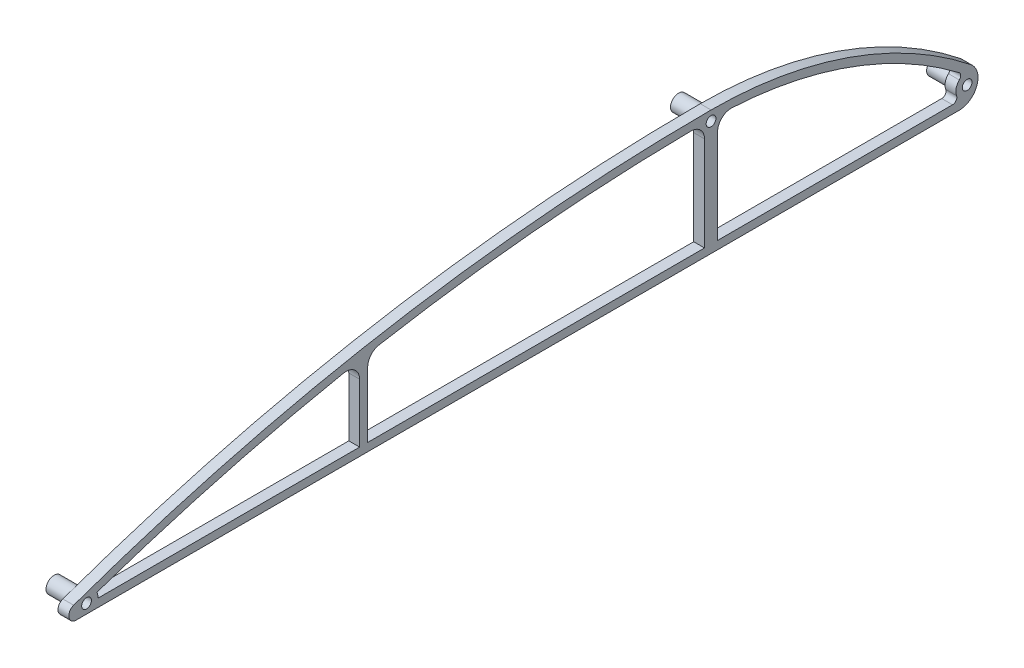
SolidWorks part; units mm, degrees
other "Marquage1"
sketch "Esquisse8" plane through (8, 0, -172.8424) normal (1, 0, 0) x (0, 0, -1)
other "Marquage2"
sketch "Esquisse10" plane through (-6, 20, -172.8424) normal (-0.8365, 0.2588, -0.483) x (-0.5, 0, 0.866)
other "Marquage3"
sketch "Esquisse11" plane through (0, 0, 0) normal (-0.0501, -0.1345, 0.9896) x (0.9942, 0.0873, 0.0622)
ref_plane "Plan de face" through (0, 0, 0) normal (0, 0, 1) x (1, 0, 0)
ref_plane "Plan de dessus" through (0, 0, 0) normal (0, 1, 0) x (1, 0, 0)
ref_plane "Plan de droite" through (0, 0, 0) normal (1, 0, 0) x (0, 0, -1)
sketch "Esquisse2" plane through (0, 0, 0) normal (1, 0, 0) x (0, 0, -1)
  line L0 (0, 0) -> (170.8732, 0)
  arc A1 (173.0499, 6.2408) -> (125, 23) centre (125, -54.2609) ccw
  arc A3 (170.8732, 0) -> (173.0499, 6.2408) centre (170.8732, 3.5) ccw
  arc A4 (125, 23) -> (0, 0) centre (125, -328.1739) ccw
  point P10 (180, 0)
  dimension "D1" = 180
  dimension "D2" = 3.5
  dimension "D3" = 23
  dimension "D4" = 55
extrude "Boss.-Extru.1" add sketch "Esquisse2" along normal blind 2
sketch "Esquisse4" plane through (2, 0, 0) normal (1, 0, 0) x (0, 0, -1)
  line L0 (9.5, 0) -> (9.5, 3.4627) construction
  line L1 (0, 0) -> (9.5, 1.7314) construction
  line L10 (174.369, 3.3283) -> (172.369, 3.3283) construction
  line L11 (0, 0) -> (170.8732, 0) construction
  circle A6 centre (125, 21.2) radius 0.9
  circle A12 centre (172.369, 3.3283) radius 0.9
  arc A13 (170.8732, 0) -> (173.0499, 6.2408) centre (170.8732, 3.5) ccw construction
  circle A15 centre (9.5, 1.7314) radius 0.9
  arc A16 (125, 23) -> (0, 0) centre (125, -328.1739) ccw construction
  dimension "D1" = 1.8
  dimension "D2" = 1.8
  dimension "D7" = 1.8
  dimension "D3" = 1.8
  dimension "D4" = 9.5
  dimension "D6" = 2
extrude "Enlèv. mat.-Extru.2" cut sketch "Esquisse4" against normal through all
sketch "Esquisse9" plane through (0, 0, 0) normal (1, 0, 0) x (0, 0, -1)
  line L26 (126.214, 1.5) -> (171.3359, 1.5)
  line L35 (8.4369, 1.5) -> (170.8732, 1.5)
  line L36 (11.5872, 1.5) -> (60, 1.5)
  line L40 (61.5, 1.5) -> (123.786, 1.5)
  line L42 (60, 1.5) -> (60, 15.4055)
  line L44 (61.5, 1.5) -> (61.5, 15.6859)
  line L45 (123.786, 21.4979) -> (123.786, 1.5)
  line L46 (126.214, 21.4979) -> (126.214, 1.5)
  arc A20 (60, 15.4055) -> (11.4359, 2.5451) centre (125, -328.1739) ccw
  circle A21 centre (125, 21.2) radius 0.9 construction
  circle A22 centre (9.5, 1.7314) radius 0.9 construction
  arc A23 (173.0499, 6.2408) -> (125, 23) centre (125, -54.2609) ccw construction
  arc A25 (171.778, 5.3435) -> (171.3359, 1.5) centre (172.369, 3.3283) ccw
  circle A26 centre (172.369, 3.3283) radius 0.9 construction
  arc A35 (170.8732, 1.5) -> (172.117, 5.0662) centre (170.8732, 3.5) ccw
  arc A39 (172.117, 5.0662) -> (125, 21.5) centre (125, -54.2609) ccw
  arc A40 (125, 21.5) -> (8.4369, 1.5) centre (125, -328.1739) ccw
  arc A42 (171.778, 5.3435) -> (126.214, 21.4979) centre (125, -54.2609) ccw
  arc A43 (123.786, 21.4979) -> (61.5, 15.6859) centre (125, -328.1739) ccw
  arc A54 (11.5872, 1.5) -> (11.4359, 2.5451) centre (9.5, 1.7314) ccw
  dimension "D1" = 1.5
  dimension "D2" = 1.25
  dimension "D3" = 1.2
  dimension "D5" = 1.25
  dimension "D4" = 1.2
  dimension "D6" = 1.5
  dimension "D7" = 60
extrude "Enlèv. mat.-Extru.3" cut sketch "Esquisse9" along normal blind 4
fillet "Congé2" radius 1.35 1 edges at (1, 0, 0)
fillet "Congé3" radius 2.5 4 edges at (1, 21.4979, -126.214) (1, 21.4979, -123.786) (1, 15.4055, -60) (1, 15.6859, -61.5)
fillet "Congé4" radius 0.8 2 edges at (1, 1.5, -171.3359) (1, 5.3435, -171.778)
sketch "Esquisse12" plane through (2, 0, 0) normal (1, 0, 0) x (0, 0, -1)
  line L0 (125, 21.2) -> (123.7425, 18.5159)
  line L1 (125, 21.2) -> (126.2458, 18.5159)
  line L2 (9.5, 1.7314) -> (7.8642, -1.7766)
  line L3 (9.5, 1.7314) -> (11.1358, -1.7766)
  line L4 (172.369, 3.3283) -> (171.2396, 0.9065)
  line L5 (172.369, 3.3283) -> (173.4983, 0.9065)
  arc A0 (125.3789, 20.3836) -> (124.6182, 20.385) centre (125, 21.2) ccw
  circle A1 centre (125, 21.2) radius 0.9 construction
  arc A2 (125.6315, 19.8394) -> (124.3636, 19.8417) centre (125, 21.2) ccw
  arc A3 (123.786, 18.9801) -> (121.2593, 21.48) centre (121.286, 18.9801) ccw construction
  arc A4 (128.8407, 21.4102) -> (126.214, 18.9134) centre (128.714, 18.9134) ccw construction
  arc A5 (9.8804, 0.9157) -> (9.1196, 0.9157) centre (9.5, 1.7314) ccw
  circle A6 centre (9.5, 1.7314) radius 0.9 construction
  arc A7 (10.1339, 0.3719) -> (8.8661, 0.3719) centre (9.5, 1.7314) ccw
  arc A8 (173.0029, 1.9689) -> (171.735, 1.9689) centre (172.369, 3.3283) ccw
  arc A9 (172.7493, 2.5127) -> (171.9886, 2.5127) centre (172.369, 3.3283) ccw
  circle A10 centre (172.369, 3.3283) radius 0.9 construction
  circle M5 centre (172.369, 3.3283) radius 0.9
  circle M6 centre (125, 21.2) radius 0.9
  circle M7 centre (9.5, 1.7314) radius 0.9
  dimension "D1" = 3
  dimension "D3" = 3
  dimension "D5" = 3
  dimension "D2" = 50
  dimension "D4" = 50
  dimension "D6" = 50
extrude "Boss.-Extru.2" add sketch "Esquisse12" against normal blind 6 contours L5 A8 L4 M5 | L1 A2 L0 M6 | L3 A7 L2 M7 region at (2, 20.1309, -124.4534) region at (2, 0.6613, -8.9553) region at (2, 2.2583, -171.8243)
